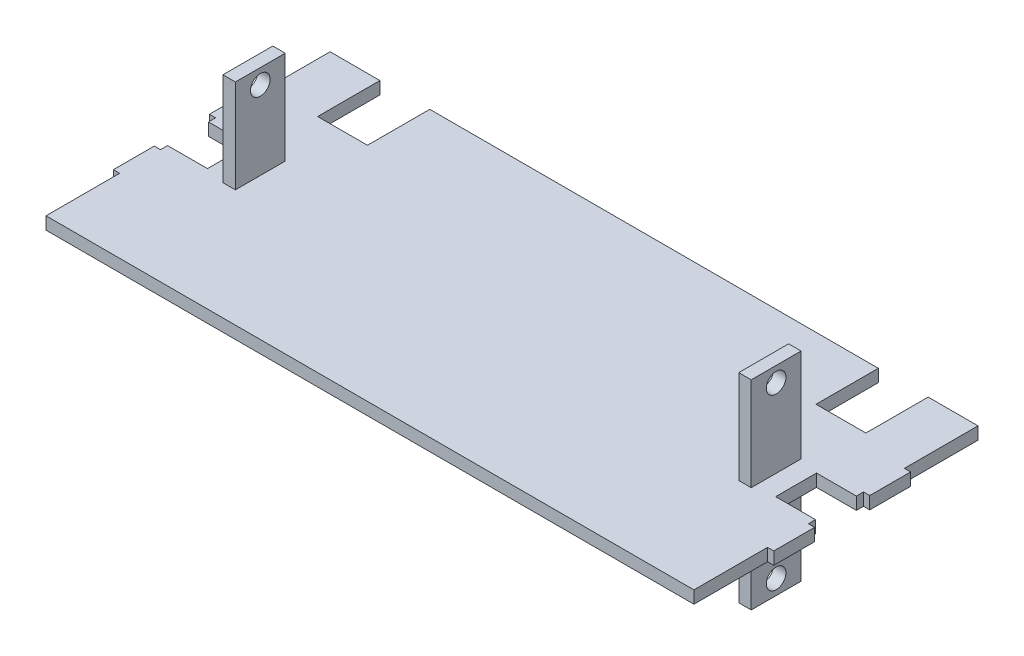
SolidWorks part; units mm, degrees
ref_plane "Front Plane" through (0, 0, 0) normal (0, 0, 1) x (1, 0, 0)
ref_plane "Top Plane" through (0, 0, 0) normal (0, 1, 0) x (1, 0, 0)
ref_plane "Right Plane" through (0, 0, 0) normal (1, 0, 0) x (0, 0, -1)
sketch "Sketch1" plane through (0, 0, 0) normal (0, 1, 0) x (1, 0, 0)
  line L0 (0, 72.39) -> (0, -72.39) construction
  line L1 (165.1, -72.39) -> (-165.1, -72.39)
  line L2 (165.1, -72.39) -> (165.1, -34.8747)
  line L3 (165.1, 72.39) -> (139.7, 72.39)
  line L4 (-165.1, -72.39) -> (-165.1, -34.8747)
  line L5 (165.1, -72.39) -> (-165.1, 72.39) construction
  line L6 (165.1, 72.39) -> (-165.1, -72.39) construction
  line L7 (165.1, 10.414) -> (144.78, 10.414)
  line L9 (165.1, -10.414) -> (144.78, -10.414)
  line L10 (144.78, 10.414) -> (144.78, -10.414)
  line L11 (-139.7, 72.39) -> (-165.1, 72.39)
  line L13 (-165.1, -10.414) -> (-144.78, -10.414)
  line L14 (-144.78, 10.414) -> (-144.78, -10.414)
  line L15 (-165.1, 10.414) -> (-144.78, 10.414)
  line L17 (-127, 0) -> (127, 0) construction
  line L18 (-165.1, 14.0467) -> (-168.275, 14.0467)
  line L20 (-165.1, 34.8747) -> (-168.275, 34.8747)
  line L21 (-168.275, 14.0467) -> (-168.275, 34.8747)
  line L22 (-165.1, -34.8747) -> (-168.275, -34.8747)
  line L23 (-168.275, -14.0467) -> (-168.275, -34.8747)
  line L24 (-165.1, -14.0467) -> (-168.275, -14.0467)
  line L27 (165.1, -14.0467) -> (168.275, -14.0467)
  line L28 (168.275, -14.0467) -> (168.275, -34.8747)
  line L29 (165.1, -34.8747) -> (168.275, -34.8747)
  line L30 (165.1, 34.8747) -> (168.275, 34.8747)
  line L31 (168.275, 14.0467) -> (168.275, 34.8747)
  line L32 (165.1, 14.0467) -> (168.275, 14.0467)
  line L34 (-165.1, 34.8747) -> (-165.1, 72.39)
  line L35 (-165.1, -14.0467) -> (-165.1, -10.414)
  line L36 (165.1, 34.8747) -> (165.1, 72.39)
  line L37 (165.1, -14.0467) -> (165.1, -10.414)
  line L38 (-165.1, 10.414) -> (-165.1, 14.0467)
  line L39 (165.1, 10.414) -> (165.1, 14.0467)
  line L40 (-139.7, 72.39) -> (-139.7, 40.64)
  line L41 (-139.7, 40.64) -> (-114.3, 40.64)
  line L42 (-114.3, 72.39) -> (-114.3, 40.64)
  line L44 (114.3, 72.39) -> (114.3, 40.64)
  line L45 (114.3, 40.64) -> (139.7, 40.64)
  line L46 (139.7, 72.39) -> (139.7, 40.64)
  line L47 (114.3, 72.39) -> (-114.3, 72.39)
  point P0 (0, 0)
  point P6 (127, 0)
  dimension "D1" = 330.2
  dimension "D2" = 144.78
  dimension "D3" = 20.828
  dimension "D5" = 3.175
  dimension "D6" = 20.828
  dimension "D4" = 20.32
  dimension "D7" = 31.75
  dimension "D8" = 25.4
  dimension "D9" = 25.4
  dimension "D10" = 31.75
  dimension "D12" = 25.4
  dimension "D11" = 25.4
extrude "Boss-Extrude1" add sketch "Sketch1" along normal mid plane 6.35
sketch "Sketch2" plane through (0, 0, 0) normal (0, 1, 0) x (1, 0, 0)
  line L0 (-144.78, 10.414) -> (-144.78, -10.414) construction
  line L1 (128.27, -12.7) -> (134.62, -12.7)
  line L2 (128.27, -12.7) -> (128.27, 12.7)
  line L3 (128.27, 12.7) -> (134.62, 12.7)
  line L4 (134.62, -12.7) -> (134.62, 12.7)
  line L5 (128.27, -12.7) -> (134.62, 12.7) construction
  line L6 (128.27, 12.7) -> (134.62, -12.7) construction
  line L9 (-128.27, -12.7) -> (-128.27, 12.7)
  line L10 (-128.27, 12.7) -> (-134.62, 12.7)
  line L11 (-134.62, -12.7) -> (-134.62, 12.7)
  line L12 (-128.27, -12.7) -> (-134.62, -12.7)
  line L13 (144.78, -10.414) -> (144.78, 10.414) construction
  point P0 (131.445, 0)
  point P10 (144.78, 0)
  dimension "D1" = 10.16
  dimension "D2" = 10.16
  dimension "D3" = 25.4
  dimension "D4" = 25.4
  dimension "D5" = 6.35
  dimension "D6" = 6.35
  dimension "D7" = 6.35
extrude "Boss-Extrude2" add sketch "Sketch2" along normal mid plane 101.6
sketch "Sketch3" plane through (-134.62, 0, 0) normal (-1, 0, 0) x (0, 0, 1)
  line L0 (-12.7, 50.8) -> (12.7, 50.8) construction
  line L1 (-12.7, -50.8) -> (12.7, -50.8) construction
  circle A0 centre (0, 43.18) radius 5.0038
  circle A1 centre (0, -43.18) radius 5.0038
  point P4 (0, 50.8)
  dimension "D1" = 10.0076
  dimension "D2" = 10.0076
  dimension "D3" = 7.62
  dimension "D4" = 7.62
extrude "Cut-Extrude1" cut sketch "Sketch3" against normal through all both and the other way through all
equation "\"length\"=13"
equation "\"width\"= 5.7"
equation "\"height\"= 0.25"
equation "\"D1@Sketch1\"=\"length\""
equation "\"D2@Sketch1\"=\"width\""
equation "\"eyebolt width\"= 0.82"
equation "\"eyebolt length\"= 0.8"
equation "\"D3@Sketch1\"=\"eyebolt width\""
equation "\"D4@Sketch1\"=\"eyebolt length\""
equation "\"lead screw holder height\"= 2.76"
equation "\"lead screw diameter\"=0.394"
equation "\"D1@Sketch3\"=\"lead screw diameter\""
equation "\"distance from holders to board\"=0.4"
equation "\"D2@Sketch3\"=\"lead screw diameter\""
